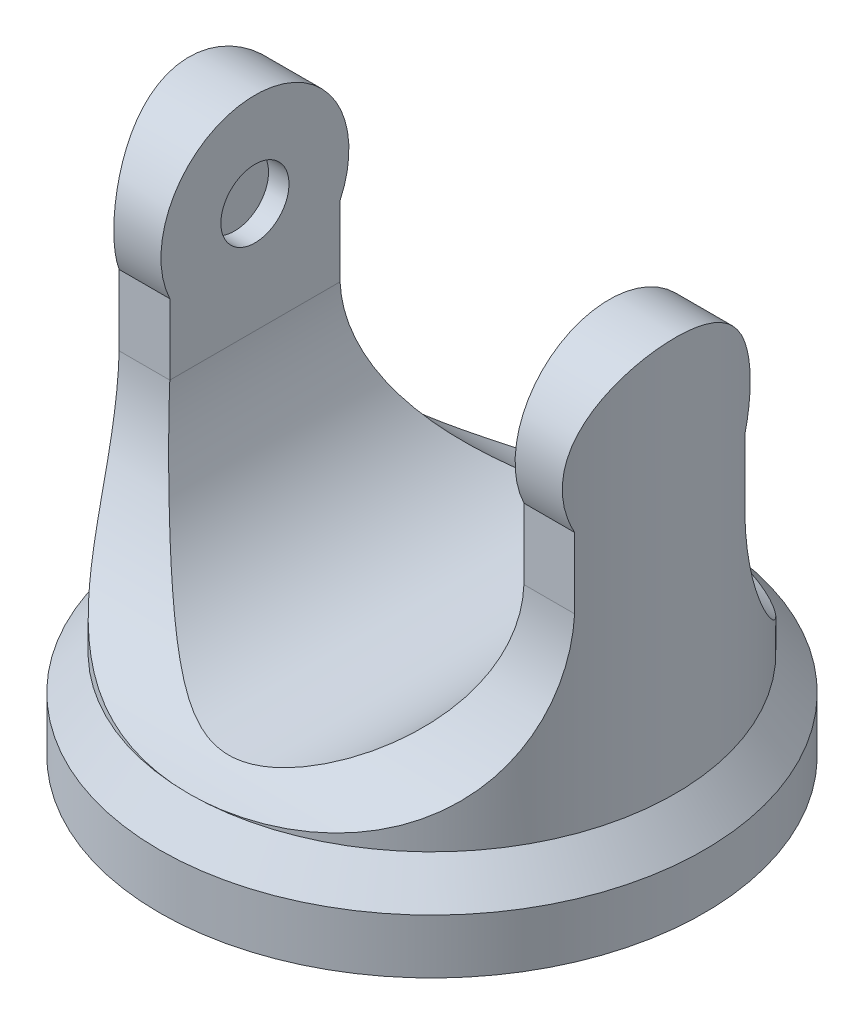
SolidWorks part; units mm, degrees
ref_plane "前视基准面" through (0, 0, 0) normal (0, 0, 1) x (1, 0, 0)
ref_plane "上视基准面" through (0, 0, 0) normal (0, 1, 0) x (1, 0, 0)
ref_plane "右视基准面" through (0, 0, 0) normal (1, 0, 0) x (0, 0, -1)
sketch "草图1" plane through (0, 0, 0) normal (0, 1, 0) x (1, 0, 0)
  circle A0 centre (0, 0) radius 40
  dimension "D1" = 80
extrude "凸台-拉伸1" add sketch "草图1" along normal blind 13
ref_axis "基准轴1" through (0, 13, 0) along (0, -1, 0)
sketch "草图2" plane through (0, 0, 0) normal (0, 0, 1) x (1, 0, 0)
  line L0 (-35.7, 13) -> (35.7, 13) construction
  line L1 (40, 13) -> (-40, 13) construction
  line L2 (-40, 0) -> (-40, 8) construction
  line L3 (-40, 13) -> (-40, 0) construction
  line L4 (-35.7, 13) -> (-40, 8)
  line L5 (-40, 8) -> (-40, 13)
  line L6 (-40, 13) -> (-35.7, 13)
  point P5 (0, 13)
  dimension "D1" = 71.4
  dimension "D2" = 8
revolve "切除-旋转1" cut sketch "草图2" angle 360 about axis through (0, 13, 0) along (0, -1, 0)
sketch "草图3" plane through (0, 13, 0) normal (0, 1, 0) x (1, 0, 0)
  circle A0 centre (0, 0) radius 35.7
extrude "凸台-拉伸2" add sketch "草图3" along normal blind 58
sketch "草图4" plane through (0, 0, 0) normal (1, 0, 0) x (0, 0, -1)
  line L0 (0, 13) -> (0, 0) construction
  line L1 (35.7, 71) -> (-35.7, 71) construction
  line L2 (-12.5, 41) -> (12.5, 41) construction
  line L3 (-12.5, 41) -> (-12.5, 51.3528)
  line L4 (12.5, 41) -> (12.5, 51.3528)
  line L5 (0, 71) -> (-35.7, 71)
  line L6 (-35.7, 71) -> (-35.7, 13)
  line L7 (0, 71) -> (35.7, 71)
  line L8 (35.7, 71) -> (35.7, 13)
  arc A0 (12.5, 51.3528) -> (-12.5, 51.3528) centre (0, 57.2) ccw
  arc A1 (-12.5, 41) -> (-35.7, 13) centre (-42.475, 42.225) cw
  arc A2 (12.5, 41) -> (35.7, 13) centre (42.475, 42.225) ccw
  point P10 (0, 41)
  dimension "D1" = 27.6
  dimension "D4" = 30
  dimension "D5" = 30
  dimension "D2" = 25
  dimension "D3" = 30
extrude "切除-拉伸1" cut sketch "草图4" against normal blind 58 and the other way blind 58 contours A1 L3 A0 L5 L6 | L4 A2 L8 L7 A0 region at (0, 45.7472, 24.6643) region at (0, 45.7472, -24.6643)
sketch "草图5" plane through (0, 0, 0) normal (0, 0, 1) x (1, 0, 0)
  line L0 (-26, 41) -> (26, 41) construction
  line L1 (33.4401, 41) -> (-33.4401, 41) construction
  line L2 (-26, 41) -> (-26, 71)
  line L3 (35.7, 71) -> (-35.7, 71) construction
  line L4 (26, 41) -> (26, 71)
  line L5 (-26, 71) -> (26, 71)
  line L6 (0, 13) -> (0, 15)
  line L7 (0, 13) -> (0, 0) construction
  arc A0 (-26, 41) -> (26, 41) centre (0, 41) ccw
  point P3 (0, 41)
  dimension "D1" = 52
  dimension "D2" = 2
extrude "切除-拉伸2" cut sketch "草图5" against normal blind 58 and the other way blind 58 contours L2 L0 L4 L5 | L0 A0 region at (0, 56, 0) region at (0, 29.9653, 0)
sketch "草图6" plane through (26, 0, 0) normal (-1, 0, 0) x (0, 0, 1)
  circle A0 centre (0, 57.2) radius 5
  dimension "D1" = 10
extrude "切除-拉伸3" cut sketch "草图6" against normal blind 3
mirror "镜向1" about plane through (0, 0, 0) normal (1, 0, 0) of "切除-拉伸3"
